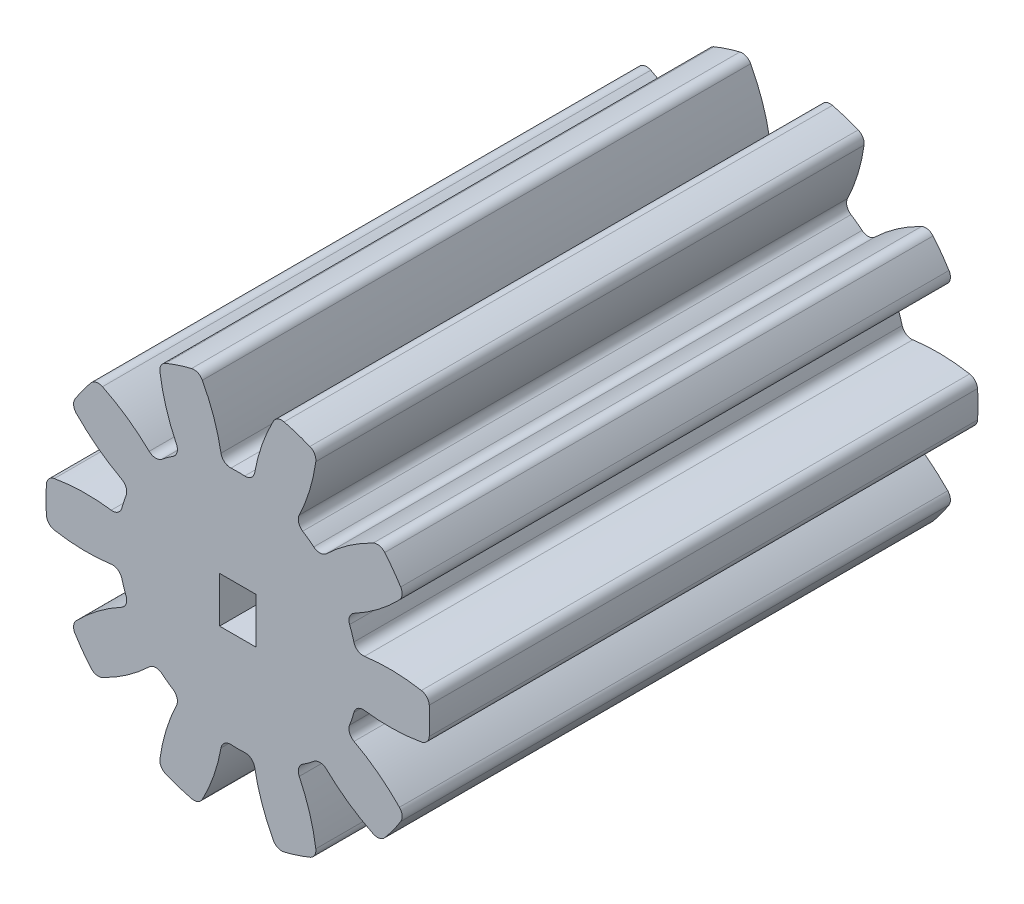
SolidWorks part; units mm, degrees
ref_plane "Front Plane" through (0, 0, 0) normal (0, 0, 1) x (1, 0, 0)
ref_plane "Top Plane" through (0, 0, 0) normal (0, 1, 0) x (1, 0, 0)
ref_plane "Right Plane" through (0, 0, 0) normal (1, 0, 0) x (0, 0, -1)
sketch "Sketch1" plane through (0, 0, 0) normal (0, 0, 1) x (1, 0, 0)
  circle A0 centre (0, 0) radius 17.5 construction
  circle A1 centre (0, 0) radius 21
  circle A2 centre (0, 0) radius 5
  dimension "D1" = 35
  dimension "D2" = 42
  dimension "D3" = 10
extrude "Boss-Extrude1" add sketch "Sketch1" along normal mid plane 60
sketch "Sketch2" plane through (0, 0, 0) normal (0, 0, 1) x (1, 0, 0)
  line L0 (0, 0) -> (0, 21) construction
  line L1 (0, 0) -> (12.3435, 16.9894) construction
  line L2 (0, 0) -> (6.4894, 19.9722) construction
  line L3 (-1.6959, 13.015) -> (0, 0) construction
  line L4 (-2.7376, 17.2845) -> (2.7376, 17.2845) construction
  line L5 (2.7376, 17.2845) -> (7.9448, 15.5926) construction
  line L6 (-3.9533, 20.6245) -> (0, 9.763) construction
  arc A0 (1.6959, 13.015) -> (-1.6959, 13.015) centre (0, 0) ccw
  circle A1 centre (0, 0) radius 14 construction
  circle A2 centre (0, 0) radius 21 construction
  arc A3 (-4.2771, 20.5598) -> (-1.6959, 13.015) centre (-21.5903, 10.4227) cw
  circle A4 centre (0, 0) radius 21 construction
  arc A5 (4.2771, 20.5598) -> (1.6959, 13.015) centre (21.5903, 10.4227) ccw
  circle A6 centre (0, 0) radius 17.5 construction
  arc A7 (4.0558, 12.4826) -> (1.6959, 13.015) centre (0, 0) ccw construction
  arc A8 (7.7147, 10.6183) -> (4.0558, 12.4826) centre (0, 0) ccw construction
  arc A9 (-1.6959, 13.015) -> (7.7147, 10.6183) centre (0, 0) ccw construction
  arc A10 (4.2771, 20.5598) -> (-4.2771, 20.5598) centre (0, 0) ccw
  arc A11 (-4.2771, 20.5598) -> (12.3435, 16.9894) centre (0, 0) ccw construction
  arc A12 (12.3435, 16.9894) -> (6.4894, 19.9722) centre (0, 0) ccw construction
  arc A13 (6.4894, 19.9722) -> (4.2771, 20.5598) centre (0, 0) ccw construction
  dimension "D1" = 36
  dimension "D2" = 7
  dimension "D3" = 7.875
  dimension "D4" = 0.875
  dimension "D5" = 20
extrude "Cut-Extrude1" cut sketch "Sketch2" against normal through all both and the other way through all
fillet "Fillet1" radius 1.05 4 edges at (1.6959, 13.015, 0) (-1.6959, 13.015, 0) (-4.2771, 20.5598, 0) (4.2771, 20.5598, 0)
pattern_circular "CirPattern1" count 10 over 360 about axis through (0, 0, 30) along (0, 0, -1) of "Fillet1", "Cut-Extrude1"
ref_axis "Axis1" through (0, 0, 30) along (0, 0, -1)
sketch "Sketch3" plane through (0, 0, -30) normal (0, 0, -1) x (-1, 0, 0)
  circle A0 centre (0, 0) radius 6.3325
extrude "Boss-Extrude2" add sketch "Sketch3" against normal blind 60
sketch "Sketch4" plane through (0, 0, 30) normal (0, 0, 1) x (1, 0, 0)
  line L0 (0, 0) -> (-3.511, 0) construction
  line L1 (-2, 2.5) -> (2, 2.5)
  line L2 (-2, 2.5) -> (-2, -2.5)
  line L3 (-2, -2.5) -> (2, -2.5)
  line L4 (2, 2.5) -> (2, -2.5)
  line L5 (-2, 2.5) -> (2, -2.5) construction
  line L6 (-2, -2.5) -> (2, 2.5) construction
  dimension "D1" = 5
  dimension "D2" = 4
  dimension "D3" = 2.5
  dimension "D4" = 2
extrude "Cut-Extrude2" cut sketch "Sketch4" against normal blind 5
sketch "Sketch5" plane through (0, 0, -30) normal (0, 0, -1) x (-1, 0, 0)
  circle A0 centre (0, 0) radius 7.5
  dimension "D1" = 15
extrude "Cut-Extrude3" cut sketch "Sketch5" against normal blind 20
equation "\"m\"= 3.5"
equation "\"N\"= 10"
equation "\"angle\"= 20"
equation "\"D1@Sketch1\"=\"m\" * \"N\""
equation "\"D2@Sketch1\"=( \"N\" + 2 ) * \"m\" "
equation "\"D1@Sketch2\"=360 / \"N\""
equation "\"D2@Sketch2\"= \"m\" * 2"
equation "\"D3@Sketch2\"= \"m\" * if( \"m\" => 1.25,2.25,2.4 )"
equation "\"D1@Fillet1\"= 0.3 * \"m\""
equation "\"D1@CirPattern1\"= \"N\""
equation "\"D1\"= \"m\""
